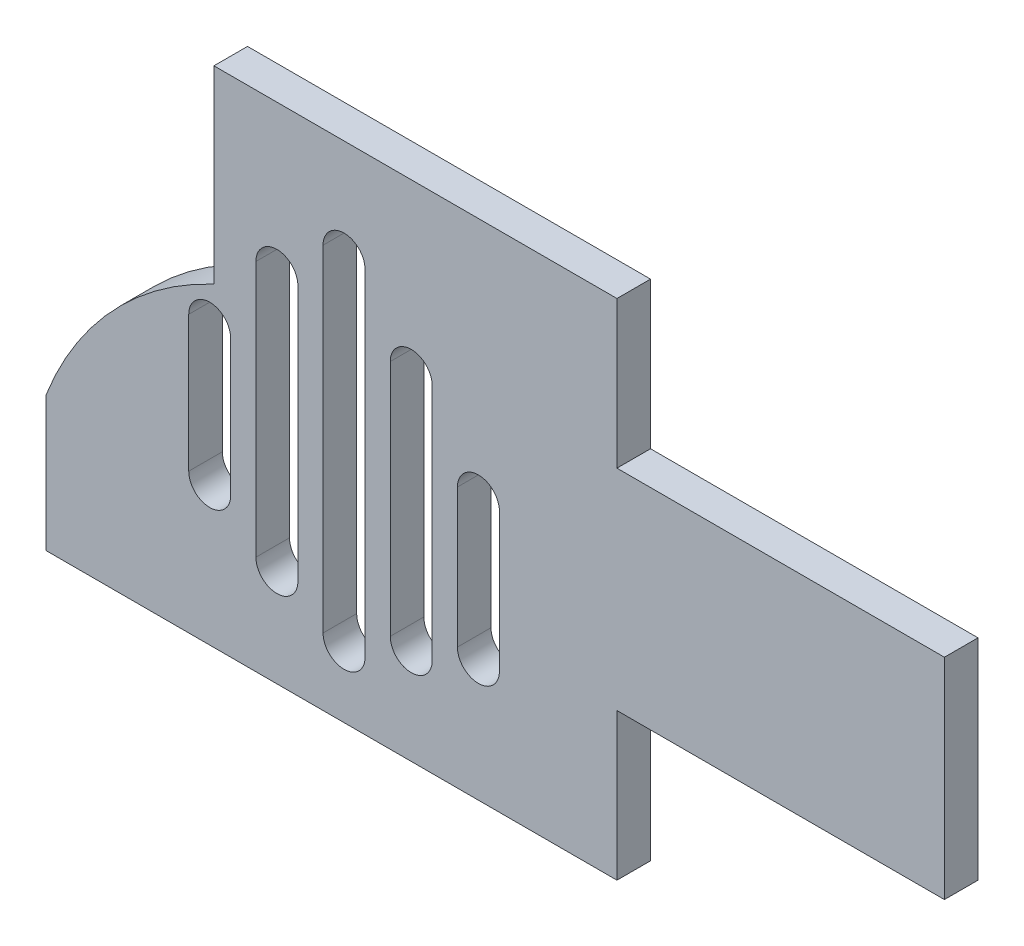
SolidWorks part; units mm, degrees
ref_plane "Front Plane" through (0, 0, 0) normal (0, 0, 1) x (1, 0, 0)
ref_plane "Top Plane" through (0, 0, 0) normal (0, 1, 0) x (1, 0, 0)
ref_plane "Right Plane" through (0, 0, 0) normal (1, 0, 0) x (0, 0, -1)
sketch "Sketch1" plane through (0, 0, 0) normal (0, 0, 1) x (1, 0, 0)
  line L0 (-4.1373, 38.9941) -> (-4.1373, -1.0059)
  line L6 (30.8627, 33.4941) -> (69.8627, 33.4941)
  line L9 (0.8627, 38.9941) -> (0.8627, -1.0059)
  line L12 (-12.1373, 33.3124) -> (-12.1373, 2.8098)
  line L15 (-7.1373, 33.3124) -> (-7.1373, 2.8098)
  line L18 (-15.1373, 23.8613) -> (-15.1373, 7.6834)
  line L21 (30.8627, 8.4941) -> (69.8627, 8.4941)
  line L26 (-37.1373, 7.0374) -> (-37.1373, -9.0059)
  line L62 (-17.1373, 50.9941) -> (-17.1373, 28.4723)
  line L66 (30.8627, 50.9941) -> (30.8627, 33.4941)
  line L68 (69.8627, 33.4941) -> (69.8627, 8.4941)
  line L70 (30.8627, 8.4941) -> (30.8627, -9.0059)
  line L71 (30.8627, 50.9941) -> (-17.1373, 50.9941)
  line L72 (30.8627, -9.0059) -> (-37.1373, -9.0059)
  line L75 (-20.1373, 23.8613) -> (-20.1373, 7.6834)
  line L77 (3.8627, 30.9941) -> (3.8627, 2.6474)
  line L79 (8.8627, 30.9941) -> (8.8627, 2.6474)
  line L80 (11.8627, 22.0483) -> (11.8627, 5.5385)
  line L81 (16.8627, 22.0483) -> (16.8627, 5.5385)
  circle A13 centre (-1.6373, 38.9941) radius 2.5 construction
  circle A14 centre (-1.6373, -1.0059) radius 2.5 construction
  arc A15 (-4.1373, 38.9941) -> (0.8627, 38.9941) centre (-1.6373, 38.9941) cw
  arc A16 (0.8627, -1.0059) -> (-4.1373, -1.0059) centre (-1.6373, -1.0059) cw
  circle A17 centre (6.3627, 30.9941) radius 2.5 construction
  circle A18 centre (6.3627, 2.6474) radius 2.5 construction
  circle A19 centre (-9.6373, 33.3124) radius 2.5 construction
  circle A20 centre (-9.6373, 2.8098) radius 2.5 construction
  circle A21 centre (-17.6373, 23.8613) radius 2.5 construction
  circle A22 centre (-17.6373, 7.6834) radius 2.5 construction
  circle A23 centre (14.3627, 22.0483) radius 2.5 construction
  circle A24 centre (14.3627, 5.5385) radius 2.5 construction
  arc A27 (-12.1373, 33.3124) -> (-7.1373, 33.3124) centre (-9.6373, 33.3124) cw
  arc A28 (-15.1373, 23.8613) -> (-20.1373, 23.8613) centre (-17.6373, 23.8613) ccw
  arc A29 (-20.1373, 7.6834) -> (-15.1373, 7.6834) centre (-17.6373, 7.6834) ccw
  arc A30 (-12.1373, 2.8098) -> (-7.1373, 2.8098) centre (-9.6373, 2.8098) ccw
  arc A31 (3.8627, 2.6474) -> (8.8627, 2.6474) centre (6.3627, 2.6474) ccw
  arc A32 (11.8627, 5.5385) -> (16.8627, 5.5385) centre (14.3627, 5.5385) ccw
  arc A33 (16.8627, 22.0483) -> (11.8627, 22.0483) centre (14.3627, 22.0483) ccw
  arc A34 (8.8627, 30.9941) -> (3.8627, 30.9941) centre (6.3627, 30.9941) ccw
  arc A35 (-17.1373, 28.4723) -> (-37.1373, 7.0374) centre (-0.5129, -7.0873) ccw
  point P0 (0, 0)
  dimension "D3" = 5
  dimension "D4" = 8
  dimension "D5" = 8
  dimension "D6" = 8
  dimension "D7" = 8
  dimension "D9" = 12
  dimension "D8" = 25
  dimension "D10" = 15.5
  dimension "D11" = 60
  dimension "D12" = 8
  dimension "D13" = 20
  dimension "D15" = 39
  dimension "D16" = 48
  dimension "D23" = 40
extrude "Boss-Extrude1" add sketch "Sketch1" along normal blind 4
sketch "Sketch2" plane through (0, 0, 0) normal (0, 0, -1) x (-1, 0, 0)
  line L0 (-69.8627, 20.9941) -> (-30.8627, 20.9941) construction
  line L1 (-69.8627, 8.4941) -> (-69.8627, 33.4941) construction
equation "\"m\"= 3mm"
